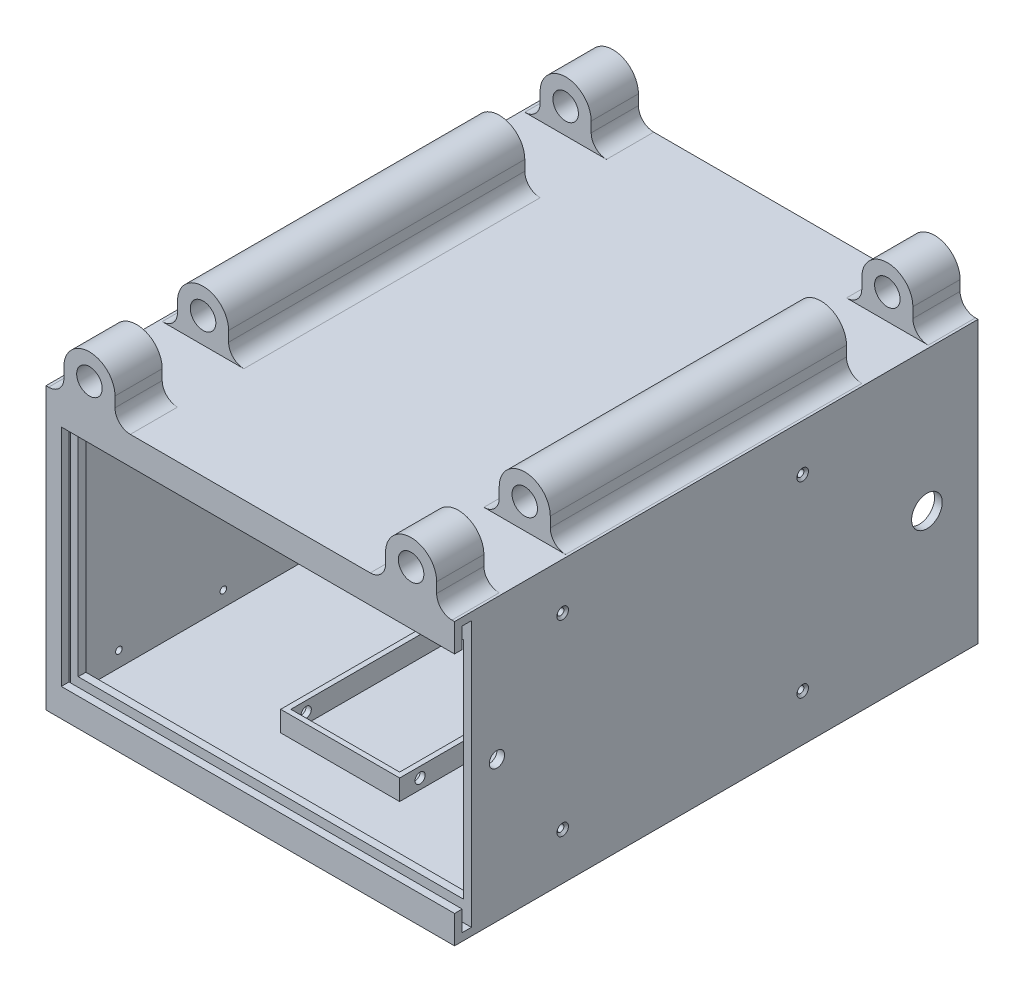
SolidWorks part; units mm, degrees
ref_plane "Front Plane" through (0, 0, 0) normal (0, 0, 1) x (1, 0, 0)
ref_plane "Top Plane" through (0, 0, 0) normal (0, 1, 0) x (1, 0, 0)
ref_plane "Right Plane" through (0, 0, 0) normal (1, 0, 0) x (0, 0, -1)
sketch "Sketch1" plane through (0, 0, 0) normal (0, 0, 1) x (1, 0, 0)
  line L0 (-92.6973, 69.85) -> (-92.6973, 82.55)
  line L1 (-101.6, 69.85) -> (-92.6973, 69.85)
  line L2 (-101.6, 69.85) -> (-101.6, -69.85)
  line L3 (-101.6, -69.85) -> (101.6, -69.85)
  line L4 (101.6, 69.85) -> (101.6, -69.85)
  line L5 (-101.6, 69.85) -> (101.6, -69.85) construction
  line L6 (-101.6, -69.85) -> (101.6, 69.85) construction
  line L7 (-67.2973, 69.85) -> (-67.2973, 82.55)
  line L8 (0, 0) -> (0, 112.2354) construction
  line L9 (67.2973, 69.85) -> (67.2973, 82.55)
  line L10 (92.6973, 69.85) -> (92.6973, 82.55)
  line L11 (-67.2973, 69.85) -> (67.2973, 69.85)
  line L12 (92.6973, 69.85) -> (101.6, 69.85)
  arc A0 (-92.6973, 82.55) -> (-67.2973, 82.55) centre (-79.9973, 82.55) cw
  circle A1 centre (-79.9973, 82.55) radius 6.35
  circle A2 centre (79.9973, 82.55) radius 6.35
  arc A3 (92.6973, 82.55) -> (67.2973, 82.55) centre (79.9973, 82.55) ccw
  point P0 (0, 0)
  dimension "D5" = 12.7
  dimension "D1" = 139.7
  dimension "D2" = 203.2
  dimension "D3" = 12.7
  dimension "D4" = 12.7
  dimension "D6" = 159.9946
  dimension "D7" = 25.4
extrude "body_extrude" add sketch "Sketch1" along normal blind 260.35
fillet "attachment_fillet" radius 7.62 4 edges at (92.6973, 69.85, 130.175) (-92.6973, 69.85, 130.175) (-67.2973, 69.85, 130.175) (67.2973, 69.85, 130.175)
sketch "Sketch4" plane through (-101.6, 0, 0) normal (-1, 0, 0) x (0, 0, 1)
  line L0 (260.35, 69.85) -> (260.35, -69.85) construction
  line L1 (251.968, 66.04) -> (256.54, 66.04)
  line L2 (251.968, 66.04) -> (251.968, -66.04)
  line L3 (251.968, -66.04) -> (256.54, -66.04)
  line L4 (256.54, 66.04) -> (256.54, -66.04)
  line L5 (256.54, 55.88) -> (260.35, 55.88)
  line L6 (256.54, 55.88) -> (256.54, -55.88)
  line L7 (256.54, -55.88) -> (260.35, -55.88)
  line L8 (260.35, 55.88) -> (260.35, -55.88)
  line L10 (260.35, -69.85) -> (0, -69.85) construction
  line L11 (130.175, 57.2601) -> (130.175, -69.85) construction
  line L12 (3.81, -55.88) -> (0, -55.88)
  line L13 (0, 55.88) -> (0, -55.88)
  line L14 (3.81, 55.88) -> (0, 55.88)
  line L15 (3.81, 55.88) -> (3.81, -55.88)
  line L16 (8.382, -66.04) -> (3.81, -66.04)
  line L17 (3.81, 66.04) -> (3.81, -66.04)
  line L18 (8.382, 66.04) -> (3.81, 66.04)
  line L19 (8.382, 66.04) -> (8.382, -66.04)
  line L31 (260.35, 69.85) -> (0, 69.85) construction
  line M14 (260.35, -69.85) -> (260.35, 69.85)
  line M16 (0, 69.85) -> (0, -69.85)
  dimension "D2" = 3.81
  dimension "D3" = 4.572
  dimension "D4" = 10.16
  dimension "D5" = 10.16
  dimension "D6" = 3.81
  dimension "D1" = 3.81
extrude "back_door_cut" cut sketch "Sketch4" against normal offset from surface (199.39 mm away) 3.81 contours L19 L18 L17 L15 L16 region at (-101.6, 0, 6.096) up to face at (101.6, 0, 130.175)
extrude "back_door_cut_2" cut sketch "Sketch4<3>" against normal offset from surface (195.58 mm away) 7.62 contours L15 L14 L12 M16 region at (-101.6, 0, 1.905) up to face at (101.6, 0, 130.175)
sketch "Sketch4<3>" plane through (-101.6, 0, 0) normal (-1, 0, 0) x (0, 0, 1) same geometry as "Sketch4"
extrude "front_door_cut" cut sketch "Sketch4<5>" against normal through all from offset 3.81 contours L4 L1 L2 L3 region at (-101.6, 0, 254.254) offset against normal yes
sketch "Sketch4<5>" plane through (-101.6, 0, 0) normal (-1, 0, 0) x (0, 0, 1) same geometry as "Sketch4"
extrude "front_door_cut_2" cut sketch "Sketch4<6>" against normal through all from offset 7.62 contours L4 L7 L5 M14 region at (-101.6, 0, 258.445) offset against normal yes
sketch "Sketch4<6>" plane through (-101.6, 0, 0) normal (-1, 0, 0) x (0, 0, 1) same geometry as "Sketch4"
sketch "Sketch5" plane through (0, 69.85, 0) normal (0, 1, 0) x (1, 0, 0)
  line L0 (-101.6, -260.35) -> (-101.6, 0) construction
  line L1 (-101.6, -23.495) -> (101.6, -23.495)
  line L2 (-101.6, -23.495) -> (-101.6, -56.515)
  line L3 (-101.6, -56.515) -> (101.6, -56.515)
  line L4 (101.6, -23.495) -> (101.6, -56.515)
  line L5 (101.6, -260.35) -> (101.6, 0) construction
  line L6 (-101.6, -130.175) -> (101.6, -130.175) construction
  line L7 (-101.6, -203.835) -> (101.6, -203.835)
  line L8 (101.6, -236.855) -> (101.6, -203.835)
  line L9 (-101.6, -236.855) -> (101.6, -236.855)
  line L10 (-101.6, -236.855) -> (-101.6, -203.835)
  dimension "D1" = 147.32
  dimension "D2" = 33.02
extrude "stopper_cut" cut sketch "Sketch5" along normal through all
sketch "Sketch6" plane through (0, 0, 8.382) normal (0, 0, -1) x (-1, 0, 0)
  line L0 (101.6, 66.04) -> (101.6, -66.04) construction
  line L1 (-97.79, 66.04) -> (97.79, 66.04)
  line L2 (-97.79, 66.04) -> (-97.79, -66.04)
  line L3 (-97.79, -66.04) -> (97.79, -66.04)
  line L4 (97.79, 66.04) -> (97.79, -66.04)
  line L5 (-97.79, 66.04) -> (97.79, -66.04) construction
  line L6 (-97.79, -66.04) -> (97.79, 66.04) construction
  line L7 (101.6, -69.85) -> (-101.6, -69.85) construction
  point P0 (0, 0)
  dimension "D2" = 3.81
  dimension "D1" = 3.81
extrude "hollow_cut" cut sketch "Sketch6" against normal up to surface (243.586 mm away) up to face at (1.905, 0, 251.968)
sketch "Sketch7" plane through (-97.79, 0, 0) normal (-1, 0, 0) x (0, 0, 1)
  line L0 (130.175, 69.85) -> (130.175, -69.85) construction
  line L1 (8.382, -66.04) -> (12.192, -66.04)
  line L2 (8.382, -66.04) -> (8.382, -55.88)
  line L3 (8.382, -55.88) -> (12.192, -55.88)
  line L4 (12.192, -66.04) -> (12.192, -55.88)
  line L5 (260.35, 69.85) -> (0, 69.85) construction
  line L6 (260.35, -69.85) -> (0, -69.85) construction
  line L7 (0, 0) -> (260.35, 0) construction
  line L8 (260.35, 69.85) -> (260.35, -69.85) construction
  line L9 (8.382, 55.88) -> (12.192, 55.88)
  line L10 (12.192, 66.04) -> (12.192, 55.88)
  line L11 (8.382, 66.04) -> (12.192, 66.04)
  line L12 (8.382, 66.04) -> (8.382, 55.88)
  line L13 (251.968, -55.88) -> (248.158, -55.88)
  line L14 (248.158, -66.04) -> (248.158, -55.88)
  line L15 (251.968, -66.04) -> (248.158, -66.04)
  line L16 (251.968, -66.04) -> (251.968, -55.88)
  line L17 (251.968, 66.04) -> (251.968, 55.88)
  line L18 (251.968, 66.04) -> (248.158, 66.04)
  line L19 (248.158, 66.04) -> (248.158, 55.88)
  line L20 (251.968, 55.88) -> (248.158, 55.88)
  dimension "D1" = 3.81
  dimension "D2" = 10.16
extrude "inner_rail_extrude" add sketch "Sketch7" against normal up to surface (195.58 mm away) up to face at (97.79, 0, 127.889)
sketch "Sketch11" plane through (0, -66.04, 0) normal (0, -1, 0) x (1, 0, 0)
  line L0 (0, 260.35) -> (0, 0) construction
  line L1 (-27.051, 213.106) -> (27.051, 213.106)
  line L2 (-27.051, 213.106) -> (-27.051, 47.244)
  line L3 (-27.051, 47.244) -> (27.051, 47.244) construction
  line L4 (27.051, 213.106) -> (27.051, 47.244)
  line L5 (-27.051, 213.106) -> (27.051, 47.244) construction
  line L6 (-27.051, 47.244) -> (27.051, 213.106) construction
  line L7 (-101.6, 260.35) -> (101.6, 260.35) construction
  line L8 (-101.6, 130.175) -> (101.6, 130.175) construction
  line L9 (-101.6, 260.35) -> (-101.6, 0) construction
  line L10 (101.6, 260.35) -> (101.6, 0) construction
  line L11 (-27.051, 47.244) -> (-27.051, 44.704)
  line L12 (-29.591, 215.646) -> (29.591, 215.646)
  line L13 (-29.591, 215.646) -> (-29.591, 44.704)
  line L14 (-29.591, 44.704) -> (29.591, 44.704) construction
  line L15 (29.591, 215.646) -> (29.591, 44.704)
  line L16 (-29.591, 215.646) -> (29.591, 44.704) construction
  line L17 (-29.591, 44.704) -> (29.591, 215.646) construction
  line L18 (27.051, 47.244) -> (27.051, 44.704)
  line L19 (-29.591, 44.704) -> (-27.051, 44.704)
  line L20 (27.051, 44.704) -> (29.591, 44.704)
  point P0 (0, 130.175)
  point P17 (0, 130.175)
  point P18 (0, 130.175)
  dimension "D1" = 54.102
  dimension "D2" = 165.862
  dimension "D3" = 2.54
  dimension "D4" = 2.54
extrude "battery_rails_extrude" add sketch "Sketch11" against normal blind 10.16
sketch "Sketch12" plane through (-29.591, 0, 0) normal (-1, 0, 0) x (0, 0, 1)
  line L0 (215.646, -60.96) -> (44.704, -60.96) construction
  line L1 (215.646, -55.88) -> (215.646, -66.04) construction
  line L2 (44.704, -55.88) -> (44.704, -66.04) construction
  line L3 (44.704, -55.88) -> (44.704, -66.04) construction
  line L4 (215.646, -55.88) -> (215.646, -66.04) construction
  circle A0 centre (54.864, -60.96) radius 2.54
  circle A1 centre (130.175, -60.96) radius 2.54
  circle A2 centre (205.486, -60.96) radius 2.54
  dimension "D5" = 10.16
  dimension "D2" = 10.16
  dimension "D1" = 5.08
  dimension "D3" = 5.08
  dimension "D4" = 5.08
extrude "battery_rail_holes_cut" cut sketch "Sketch12" against normal up to surface (59.182 mm away) up to face at (29.591, -60.96, 130.175)
hole_wizard "usrp_holes" positions "Sketch13" profile "Sketch14" countersink size "#4" standard "ANSI Inch" end condition up to next
sketch "Sketch13" plane through (101.6, 0, 0) normal (1, 0, 0) x (0, 0, -1)
  line L1 (-227.076, 49.911) -> (-72.644, 49.911) construction
  line L2 (-227.076, 49.911) -> (-227.076, -49.911) construction
  line L3 (-227.076, -49.911) -> (-72.644, -49.911) construction
  line L4 (-72.644, 49.911) -> (-72.644, -49.911) construction
  line L5 (-227.076, 49.911) -> (-72.644, -49.911) construction
  line L6 (-227.076, -49.911) -> (-72.644, 49.911) construction
  line L7 (-251.968, 0) -> (0, 0) construction
  line L8 (-251.968, 66.04) -> (-251.968, -66.04) construction
  line L10 (-149.86, 69.85) -> (-149.86, -69.85) construction
  point P102 (-149.86, 0)
  point P103 (-206.5528, 46.609)
  point P105 (-206.5528, -46.609)
  point P107 (-87.1982, -46.609)
  point P109 (-87.1982, 46.609)
  dimension "D2" = 154.432
  dimension "D3" = 99.822
  dimension "D4" = 20.5232
  dimension "D5" = 3.302
  dimension "D6" = 14.5542
  dimension "D7" = 3.302
  dimension "D1" = 102.108
sketch "Sketch14" plane through (101.6, 46.609, 87.1982) normal (0, 1, 0) x (0, 0, -1)
  line L0 (0, 0) -> (0, 3.81)
  line L1 (0, 3.81) -> (1.6319, 3.81)
  line L2 (1.6319, 3.81) -> (1.6319, 1.0284)
  line L3 (1.6319, 1.0284) -> (2.8575, 0)
  line L5 (2.8575, 0) -> (0, 0)
  line L6 (-1.632, 1.0284) -> (-2.8575, 0) construction
  line L11 (0, -6.35) -> (0, 107.95) construction
  dimension "Thru Hole Dia." = 3.2639
  dimension "Thru Hole Depth" = 3.81
  dimension "Near C'Sink Dia." = 5.715
  dimension "Near C'Sink Angle" = 100
hole_wizard "jetson_holes" positions "Sketch15" profile "Sketch16" countersink size "#4" standard "ANSI Inch" end condition up to next
sketch "Sketch15" plane through (-101.6, 0, 0) normal (-1, 0, 0) x (0, 0, 1)
  line L0 (8.382, 0) -> (260.35, 0) construction
  line L1 (8.382, 66.04) -> (8.382, -66.04) construction
  line L2 (260.35, 69.85) -> (260.35, -69.85) construction
  line L6 (162.56, 62.23) -> (241.3, 62.23) construction
  line L7 (162.56, 62.23) -> (162.56, -62.23) construction
  line L8 (162.56, -62.23) -> (241.3, -62.23) construction
  line L9 (241.3, 62.23) -> (241.3, -62.23) construction
  line L10 (162.56, 62.23) -> (241.3, -62.23) construction
  line L11 (162.56, -62.23) -> (241.3, 62.23) construction
  line L12 (201.93, 62.23) -> (201.93, -62.23) construction
  point P234 (201.93, 0)
  point P235 (175.9712, 58.4454)
  point P243 (227.8888, 58.4454)
  point P244 (227.8888, -58.4454)
  point P245 (175.9712, -58.4454)
  dimension "D1" = 19.05
  dimension "D2" = 78.74
  dimension "D3" = 124.46
  dimension "D4" = 25.9588
  dimension "D5" = 3.7846
sketch "Sketch16" plane through (-101.6, -58.4454, 175.9712) normal (0, 1, 0) x (0, 0, 1)
  line L0 (0, 0) -> (0, 3.81)
  line L1 (0, 3.81) -> (1.6319, 3.81)
  line L2 (1.6319, 3.81) -> (1.6319, 1.0284)
  line L3 (1.6319, 1.0284) -> (2.8575, 0)
  line L5 (2.8575, 0) -> (0, 0)
  line L6 (-1.6319, 1.0284) -> (-2.8575, 0) construction
  line L11 (0, -6.35) -> (0, 107.95) construction
  dimension "Thru Hole Dia." = 3.2639
  dimension "Thru Hole Depth" = 3.81
  dimension "Near C'Sink Dia." = 5.715
  dimension "Near C'Sink Angle" = 100
hole_wizard "cui_holes" positions "Sketch17" profile "Sketch18" countersink size "#4" standard "ANSI Inch" end condition up to next
sketch "Sketch17" plane through (-101.6, 0, 0) normal (-1, 0, 0) x (0, 0, 1)
  line L0 (260.35, -69.85) -> (0, -69.85) construction
  line L1 (0, -55.88) -> (0, -69.85) construction
  point P0 (99.822, -21.336)
  point P2 (38.1, -44.45)
  dimension "D1" = 23.114
  dimension "D2" = 61.722
  dimension "D3" = 25.4
  dimension "D4" = 38.1
sketch "Sketch18" plane through (-101.6, -21.336, 99.822) normal (0, 1, 0) x (0, 0, 1)
  line L0 (0, 0) -> (0, 3.81)
  line L1 (0, 3.81) -> (1.6319, 3.81)
  line L2 (1.6319, 3.81) -> (1.6319, 1.0284)
  line L3 (1.6319, 1.0284) -> (2.8575, 0)
  line L5 (2.8575, 0) -> (0, 0)
  line L6 (-1.6319, 1.0284) -> (-2.8575, 0) construction
  line L11 (0, -6.35) -> (0, 107.95) construction
  dimension "Thru Hole Dia." = 3.2639
  dimension "Thru Hole Depth" = 3.81
  dimension "Near C'Sink Dia." = 5.715
  dimension "Near C'Sink Angle" = 100
sketch "Sketch19" plane through (0, -69.85, 0) normal (0, -1, 0) x (1, 0, 0)
  line L0 (101.6, 260.35) -> (101.6, 0) construction
  line L1 (93.98, 12.192) -> (101.6, 12.192)
  line L2 (93.98, 12.192) -> (93.98, 8.382)
  line L3 (93.98, 8.382) -> (101.6, 8.382)
  line L4 (101.6, 12.192) -> (101.6, 8.382)
  line L5 (93.98, 12.192) -> (101.6, 8.382) construction
  line L6 (93.98, 8.382) -> (101.6, 12.192) construction
  line L7 (-101.6, 260.35) -> (-101.6, 0) construction
  line L8 (-93.98, 251.968) -> (-101.6, 251.968)
  line L9 (-93.98, 251.968) -> (-93.98, 248.158)
  line L10 (-93.98, 248.158) -> (-101.6, 248.158)
  line L11 (-101.6, 251.968) -> (-101.6, 248.158)
  line L12 (-93.98, 251.968) -> (-101.6, 248.158) construction
  line L13 (-93.98, 248.158) -> (-101.6, 251.968) construction
  line L14 (-101.6, 0) -> (101.6, 0) construction
  line L15 (-101.6, 260.35) -> (101.6, 260.35) construction
  point P0 (97.79, 10.287)
  point P7 (-97.79, 250.063)
  dimension "D1" = 8.382
  dimension "D2" = 8.382
  dimension "D3" = 3.81
  dimension "D4" = 3.81
  dimension "D5" = 7.62
  dimension "D6" = 7.62
extrude "inner_door_stoppers" add sketch "Sketch19" against normal up to surface (135.89 mm away) up to face at (1.905, 66.04, 254.254)
hole_wizard "terminal_block_holes" positions "Sketch20" profile "Sketch21" countersink size "#4" standard "ANSI Inch" end condition up to next
sketch "Sketch20" plane through (-101.6, 0, 0) normal (-1, 0, 0) x (0, 0, 1)
  line L6 (41.4909, 33.909) -> (60.1091, 33.909) construction
  line L7 (41.4909, 33.909) -> (41.4909, -2.286) construction
  line L8 (41.4909, -2.286) -> (60.1091, -2.286) construction
  line L9 (60.1091, 33.909) -> (60.1091, -2.286) construction
  line L10 (50.8, 33.909) -> (50.8, -2.286) construction
  line L12 (41.4909, 15.8115) -> (60.1091, 15.8115) construction
  circle A1 centre (99.822, -21.336) radius 1.6319 construction
  circle A2 centre (38.1, -44.45) radius 1.6319 construction
  point P94 (46.4185, 30.353)
  point P105 (55.1815, 1.27)
  dimension "D1" = 18.6182
  dimension "D2" = 36.195
  dimension "D3" = 3.556
  dimension "D4" = 4.9276
  dimension "D5" = 19.05
  dimension "D6" = 12.7
  dimension "D7" = 3.556
  dimension "D8" = 4.9276
sketch "Sketch21" plane through (-101.6, 1.27, 55.1815) normal (0, 1, 0) x (0, 0, 1)
  line L0 (0, 0) -> (0, 3.81)
  line L1 (0, 3.81) -> (1.6319, 3.81)
  line L2 (1.6319, 3.81) -> (1.6319, 1.0284)
  line L3 (1.6319, 1.0284) -> (2.8575, 0)
  line L5 (2.8575, 0) -> (0, 0)
  line L6 (-1.632, 1.0284) -> (-2.8575, 0) construction
  line L11 (0, -6.35) -> (0, 107.95) construction
  dimension "Thru Hole Dia." = 3.2639
  dimension "Thru Hole Depth" = 3.81
  dimension "Near C'Sink Dia." = 5.715
  dimension "Near C'Sink Angle" = 100
sketch "Sketch23" plane through (101.6, 0, 0) normal (1, 0, 0) x (0, 0, -1)
  line L0 (-251.968, 66.04) -> (-251.968, -66.04) construction
  line L1 (0, 0) -> (-251.968, 0) construction
  line L2 (0, -69.85) -> (0, 69.85) construction
  circle A0 centre (-239.268, 0) radius 3.81
  circle A1 centre (-25.4, 0) radius 7.62
  dimension "D1" = 7.62
  dimension "D3" = 15.24
  dimension "D4" = 25.4
  dimension "D2" = 12.7
extrude "marine_seal" cut sketch "Sketch23" against normal up to surface (3.81 mm away) up to face at (97.79, 0, 190.119)
equation "\"D4@Sketch1\"=\"D3@Sketch1\""
equation "\"D2@Sketch4\"=\"D1@Sketch4\""
equation "\"D4@Sketch4\"=\"D5@Sketch4\""
equation "\"D6@Sketch4\"=\"D1@Sketch4\""
equation "\"D1@back_door_cut\" = \"D1@Sketch4\""
equation "\"D1@back_door_cut_2\" = 2 * \"D1@Sketch4\""
equation "\"D19@front_door_cut\" = \"D1@Sketch4\""
equation "\"D19@front_door_cut_2\" = 2 * \"D1@Sketch4\""
equation "\"D2@Sketch6\"=\"D1@Sketch4\""
equation "\"D1@Sketch6\"=\"D1@Sketch4\""
equation "\"D1@Sketch7\"=\"D1@Sketch4\""
equation "\"D3@Sketch12\"=\"D1@Sketch12\""
equation "\"D4@Sketch12\"=\"D1@Sketch12\""
equation "\"D5@Sketch12\"=\"D2@Sketch12\""
equation "\"D4@Sketch13\"=0.743+0.5*0.13"
equation "\"D5@Sketch13\"=0.065+0.5*0.13"
equation "\"D6@Sketch13\"=0.508+0.5*0.13"
equation "\"D7@Sketch13\"=\"D5@Sketch13\""
equation "\"D5@Sketch15\"=0.084+0.13*0.5"
equation "\"D3@Sketch20\"=0.075+0.13*0.5"
equation "\"D4@Sketch20\"=0.129+0.5*0.13"
equation "\"D7@Sketch20\"=\"D3@Sketch20\""
equation "\"D8@Sketch20\"=\"D4@Sketch20\""
